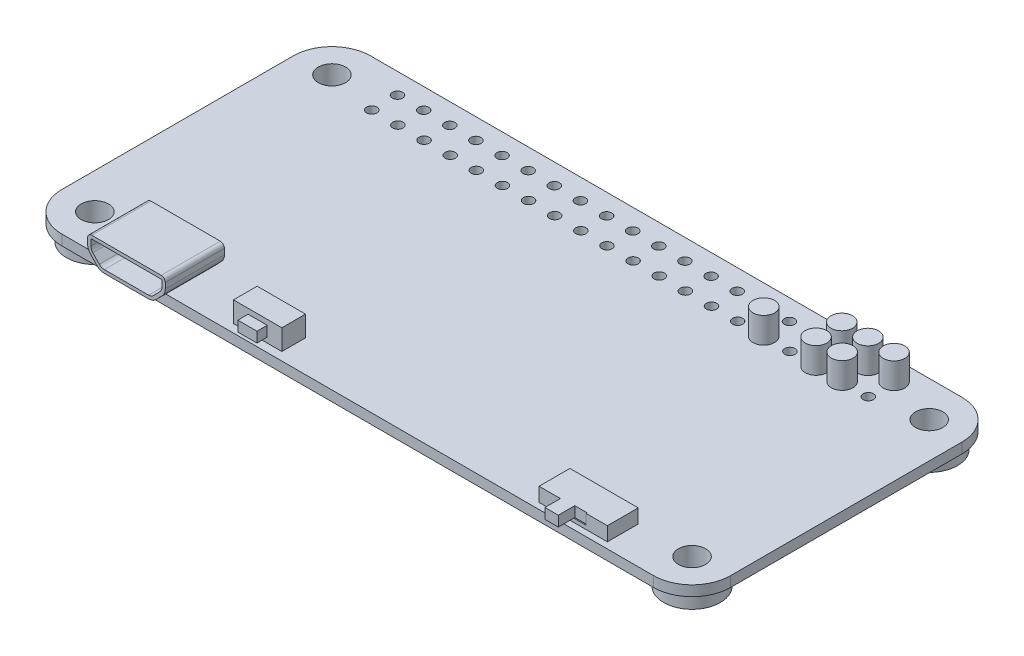
SolidWorks part; units mm, degrees
ref_plane "Front Plane" through (0, 0, 0) normal (0, 0, 1) x (1, 0, 0)
ref_plane "Top Plane" through (0, 0, 0) normal (0, 1, 0) x (1, 0, 0)
ref_plane "Right Plane" through (0, 0, 0) normal (1, 0, 0) x (0, 0, -1)
sketch "Sketch1" plane through (0, 0, 0) normal (0, 1, 0) x (1, 0, 0)
  line L1 (-28.75, 15) -> (28.75, 15)
  line L2 (-32.5, 11.25) -> (-32.5, -11.25)
  line L3 (-28.75, -15) -> (28.75, -15)
  line L4 (32.5, 11.25) -> (32.5, -11.25)
  line L5 (-32.5, 15) -> (32.5, -15) construction
  line L6 (-32.5, -15) -> (32.5, 15) construction
  arc A0 (-32.5, -11.25) -> (-28.75, -15) centre (-28.75, -11.25) ccw
  arc A1 (28.75, -15) -> (32.5, -11.25) centre (28.75, -11.25) ccw
  arc A2 (28.75, 15) -> (32.5, 11.25) centre (28.75, 11.25) cw
  arc A3 (-28.75, 15) -> (-32.5, 11.25) centre (-28.75, 11.25) ccw
  point P0 (0, 0)
  dimension "D3" = 3.75
  dimension "D1" = 65
  dimension "D2" = 30
extrude "Boss-Extrude1" add sketch "Sketch1" along normal blind 1 contours L1 A2 L4 A1 L3 A0 L2 A3
sketch "Sketch2" plane through (0, 1, 0) normal (0, 1, 0) x (1, 0, 0)
  line L0 (0, 15) -> (0, -15) construction
  line L1 (-28.75, 15) -> (28.75, 15) construction
  line L2 (-28.75, -15) -> (28.75, -15) construction
  line L3 (-32.5, 0) -> (32.5, 0) construction
  line L4 (-32.5, 11.25) -> (-32.5, -11.25) construction
  line L5 (32.5, 11.25) -> (32.5, -11.25) construction
  circle A0 centre (-29.025, 11.525) radius 1.325
  circle A2 centre (29.025, 11.525) radius 1.325
  circle A3 centre (29.025, -11.525) radius 1.325
  circle A4 centre (-29.025, -11.525) radius 1.325
  dimension "D1" = 2.65
  dimension "D2" = 2.15
  dimension "D3" = 2.15
extrude "Cut-Extrude1" cut sketch "Sketch2" against normal through all
sketch "Sketch3" plane through (0, 1, 0) normal (0, 1, 0) x (1, 0, 0)
  line L0 (-24.128, 13) -> (-24.128, 10.5) construction
  line L3 (-28.75, 15) -> (28.75, 15) construction
  line L5 (-32.5, 11.25) -> (-32.5, -11.25) construction
  circle A0 centre (-24.128, 13) radius 0.5
  circle A1 centre (-24.128, 10.5) radius 0.5
  dimension "D1" = 1
  dimension "D3" = 1.5
  dimension "D4" = 7.872
  dimension "D2" = 2.5
extrude "Cut-Extrude2" cut sketch "Sketch3" against normal through all
pattern_linear "LPattern1" count 20 spacing 2.54 along (1, 0, 0) of "Cut-Extrude2"
sketch "Sketch15" plane through (0, 0, 15) normal (0, 0, 1) x (1, 0, 0)
  line L0 (-21.225, 1) -> (-21.225, 3.6) construction
  line L1 (-28.75, 1) -> (28.75, 1) construction
  line L2 (-24.6, 3.6) -> (-17.85, 3.6)
  line L3 (-17.45, 3.2) -> (-17.45, 2.6523)
  line L4 (-17.7286, 1.9598) -> (-18.3548, 1.3075)
  line L5 (-19.0762, 1) -> (-23.3738, 1)
  line L7 (-24.7214, 1.9598) -> (-24.0952, 1.3075)
  line L8 (-25, 3.2) -> (-25, 2.6523)
  line L9 (15.325, 0) -> (15.325, 5.5788) construction
  line L10 (-28.75, 0) -> (28.75, 0) construction
  line L11 (-32.5, 1) -> (-32.5, 0) construction
  arc A0 (-18.3548, 1.3075) -> (-19.0762, 1) centre (-19.0762, 2) cw
  arc A1 (-24.0952, 1.3075) -> (-23.3738, 1) centre (-23.3738, 2) ccw
  arc A2 (-17.45, 2.6523) -> (-17.7286, 1.9598) centre (-18.45, 2.6523) cw
  arc A3 (-24.7214, 1.9598) -> (-25, 2.6523) centre (-24, 2.6523) cw
  arc A4 (-17.85, 3.6) -> (-17.45, 3.2) centre (-17.85, 3.2) cw
  arc A5 (-25, 3.2) -> (-24.6, 3.6) centre (-24.6, 3.2) cw
  point P14 (-18.65, 1)
  point P17 (-23.8, 1)
  point P20 (-17.45, 2.25)
  point P23 (-25, 2.25)
  point P26 (-17.45, 3.6)
  point P29 (-25, 3.6)
  dimension "D6" = 1
  dimension "D7" = 0.4
  dimension "D1" = 7.55
  dimension "D2" = 2.6
  dimension "D3" = 1.35
  dimension "D4" = 5.15
  dimension "D5" = 7.5
extrude "Boss-Extrude6" add sketch "Sketch15" along normal blind 1.25 and the other way blind 4.5
sketch "Sketch16" plane through (0, 0, 16.25) normal (0, 0, 1) x (1, 0, 0)
  line L30 (-18.5857, 1.5291) -> (-17.9595, 2.1814)
  line L31 (-17.77, 2.6523) -> (-17.77, 3.2)
  line L32 (-17.85, 3.28) -> (-24.6, 3.28)
  line L33 (-24.68, 3.2) -> (-24.68, 2.6523)
  line L34 (-24.4905, 2.1814) -> (-23.8643, 1.5291)
  line L35 (-23.3738, 1.32) -> (-19.0762, 1.32)
  line L36 (-18.5857, 1.5291) -> (-17.9595, 2.1814)
  line L37 (-17.77, 2.6523) -> (-17.77, 3.2)
  line L38 (-17.85, 3.28) -> (-24.6, 3.28)
  line L39 (-24.68, 3.2) -> (-24.68, 2.6523)
  line L40 (-24.4905, 2.1814) -> (-23.8643, 1.5291)
  line L41 (-23.3738, 1.32) -> (-19.0762, 1.32)
  arc A30 (-19.0762, 1.32) -> (-18.5857, 1.5291) centre (-19.0762, 2) ccw
  arc A31 (-17.9595, 2.1814) -> (-17.77, 2.6523) centre (-18.45, 2.6523) ccw
  arc A32 (-17.77, 3.2) -> (-17.85, 3.28) centre (-17.85, 3.2) ccw
  arc A33 (-24.6, 3.28) -> (-24.68, 3.2) centre (-24.6, 3.2) ccw
  arc A34 (-24.68, 2.6523) -> (-24.4905, 2.1814) centre (-24, 2.6523) ccw
  arc A35 (-23.8643, 1.5291) -> (-23.3738, 1.32) centre (-23.3738, 2) ccw
  arc A36 (-19.0762, 1.32) -> (-18.5857, 1.5291) centre (-19.0762, 2) ccw
  arc A37 (-17.9595, 2.1814) -> (-17.77, 2.6523) centre (-18.45, 2.6523) ccw
  arc A38 (-17.77, 3.2) -> (-17.85, 3.28) centre (-17.85, 3.2) ccw
  arc A39 (-24.6, 3.28) -> (-24.68, 3.2) centre (-24.6, 3.2) ccw
  arc A40 (-24.68, 2.6523) -> (-24.4905, 2.1814) centre (-24, 2.6523) ccw
  arc A41 (-23.8643, 1.5291) -> (-23.3738, 1.32) centre (-23.3738, 2) ccw
  dimension "D2" = 0.32
extrude "Cut-Extrude9" cut sketch "Sketch16" against normal blind 5.25
sketch "草图1" plane through (0, 1, 0) normal (0, 1, 0) x (1, 0, 0)
  line L0 (-32.5, 11.25) -> (-32.5, -11.25) construction
  line L1 (-12.87, -11.9) -> (-8.17, -11.9)
  line L2 (-12.87, -11.9) -> (-12.87, -14.2)
  line L3 (-12.87, -14.2) -> (-8.17, -14.2)
  line L4 (-8.17, -11.9) -> (-8.17, -14.2)
  line L5 (-28.75, -15) -> (-23.3738, -15) construction
  dimension "D1" = 4.7
  dimension "D2" = 2.3
  dimension "D3" = 19.63
  dimension "D4" = 0.8
extrude "凸台-拉伸1" add sketch "草图1" along normal blind 2
sketch "草图2" plane through (0, 0, 14.2) normal (0, 0, 1) x (1, 0, 0)
  line L0 (-12.87, 3) -> (-8.17, 3) construction
  line L5 (-11.45, 2.5) -> (-9.59, 2.5)
  line L6 (-11.45, 2.5) -> (-11.45, 1.5)
  line L7 (-11.45, 1.5) -> (-9.59, 1.5)
  line L8 (-9.59, 2.5) -> (-9.59, 1.5)
  line L9 (-11.45, 2.5) -> (-9.59, 1.5) construction
  line L10 (-11.45, 1.5) -> (-9.59, 2.5) construction
  line L11 (-8.17, 3) -> (-8.17, 1) construction
  point P0 (-10.52, 2)
  point P8 (-10.52, 3)
  point P12 (-8.17, 2)
  dimension "D1" = 1.86
  dimension "D2" = 1
extrude "凸台-拉伸2" add sketch "草图2" along normal blind 1
sketch "草图6" plane through (0, 1, 0) normal (0, 1, 0) x (1, 0, 0)
  line L0 (32.5, 11.25) -> (32.5, -11.25) construction
  line L1 (23.67, -11.4) -> (17.03, -11.4)
  line L2 (23.67, -11.4) -> (23.67, -14.4)
  line L3 (23.67, -14.4) -> (17.03, -14.4)
  line L4 (17.03, -11.4) -> (17.03, -14.4)
  line L5 (23.67, -11.4) -> (17.03, -14.4) construction
  line L6 (23.67, -14.4) -> (17.03, -11.4) construction
  line L7 (-19.0762, -15) -> (28.75, -15) construction
  point P0 (20.35, -12.9)
  dimension "D1" = 8.83
  dimension "D2" = 6.64
  dimension "D3" = 3
  dimension "D4" = 0.6
extrude "凸台-拉伸6" add sketch "草图6" along normal blind 1.36
sketch "草图7" plane through (0, 0, 14.4) normal (0, 0, 1) x (1, 0, 0)
  line L0 (17.03, 2.36) -> (23.67, 2.36) construction
  line L1 (19.1, 2.36) -> (21.6, 2.36)
  line L2 (19.1, 2.36) -> (19.1, 1.36)
  line L3 (19.1, 1.36) -> (21.6, 1.36)
  line L4 (21.6, 2.36) -> (21.6, 1.36)
  line L5 (23.67, 2.36) -> (17.03, 2.36) construction
  point P8 (20.35, 2.36)
  point P9 (20.35, 2.36)
  dimension "D1" = 1
  dimension "D2" = 2.5
extrude "切除-拉伸1" cut sketch "草图7" against normal blind 0.1
sketch "草图8" plane through (0, 0, 14.3) normal (0, 0, 1) x (1, 0, 0)
  line L0 (19.1, 2.36) -> (19.1, 1.36) construction
  line L1 (19.1, 2.36) -> (20.4, 2.36)
  line L2 (19.1, 2.36) -> (19.1, 1.36)
  line L3 (19.1, 1.36) -> (20.4, 1.36)
  line L4 (20.4, 2.36) -> (20.4, 1.36)
  line L5 (21.6, 2.36) -> (19.1, 2.36) construction
  line L6 (19.1, 1.36) -> (21.6, 1.36) construction
  dimension "D1" = 1.3
extrude "凸台-拉伸7" add sketch "草图8" along normal blind 1.6
sketch "草图9" plane through (0, 0, 0) normal (0, -1, 0) x (1, 0, 0)
  circle A0 centre (29.025, 11.525) radius 2.75
  circle A1 centre (29.025, -11.525) radius 2.75
  circle A2 centre (-29.025, 11.525) radius 2.75
  circle A3 centre (-29.025, -11.525) radius 2.75
  circle A4 centre (29.025, 11.525) radius 1.325 construction
  circle A5 centre (29.025, -11.525) radius 1.325 construction
  circle A6 centre (-29.025, 11.525) radius 1.325 construction
  circle A7 centre (-29.025, -11.525) radius 1.325 construction
  circle A8 centre (29.025, 11.525) radius 1.325
  circle A9 centre (29.025, -11.525) radius 1.325
  circle A10 centre (-29.025, 11.525) radius 1.325
  circle A11 centre (-29.025, -11.525) radius 1.325
  dimension "D1" = 5.5
extrude "凸台-拉伸8" add sketch "草图9" along normal blind 1.5
sketch "草图10" plane through (0, 1, 0) normal (0, 1, 0) x (1, 0, 0)
  circle A0 centre (24.132, 13) radius 1.05
  circle A1 centre (21.592, 13) radius 1.05
  circle A2 centre (19.052, 13) radius 1.05
  circle A3 centre (21.592, 10.5) radius 1.05
  circle A4 centre (19.052, 10.5) radius 1.05
  circle A6 centre (13.972, 10.5) radius 1.05
  dimension "D1" = 2.1
extrude "凸台-拉伸9" add sketch "草图10" along normal blind 2.5
sketch "草图11" plane through (0, 1, 0) normal (0, -1, 0) x (1, 0, 0)
  circle A0 centre (24.132, -13) radius 0.5
  circle A1 centre (21.592, -13) radius 0.5
  circle A2 centre (21.592, -10.5) radius 0.5
  circle A3 centre (19.052, -10.5) radius 0.5
  circle A5 centre (19.052, -13) radius 0.5
  circle A8 centre (13.972, -10.5) radius 0.5
extrude "凸台-拉伸10" add sketch "草图11" along normal blind 3
